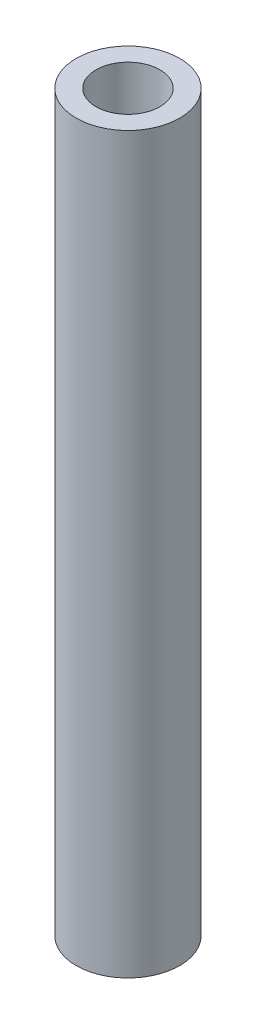
SolidWorks part; units mm, degrees
material "6063-T6"
ref_plane "Front Plane" through (0, 0, 0) normal (0, 0, 1) x (1, 0, 0)
ref_plane "Top Plane" through (0, 0, 0) normal (0, 1, 0) x (1, 0, 0)
ref_plane "Right Plane" through (0, 0, 0) normal (1, 0, 0) x (0, 0, -1)
sketch "Sketch1" plane through (0, 0, 0) normal (0, 1, 0) x (1, 0, 0)
  circle A0 centre (0, 0) radius 2.58
  circle A1 centre (0, 0) radius 5.5
  circle A2 centre (0, 0) radius 4.58 construction
  dimension "D1" = 2
  dimension "D2" = 11
  dimension "D3" = 5.16
  dimension "D4" = 9.16
extrude "Boss-Extrude1" add sketch "Sketch1" along normal blind 78
sketch "Sketch2" plane through (0, 0, 0) normal (0, -1, 0) x (1, 0, 0)
  circle A0 centre (0, 0) radius 5.5
  circle A1 centre (0, 0) radius 5.5 construction
  circle A2 centre (0, 0) radius 5.5
  point P2 (0, 0)
  point P3 (5.3485, 1.2822)
  point P4 (0, 0)
  point P5 (0, 0)
  dimension "D1" = 11
sketch "Sketch4" plane through (0, 78, 0) normal (0, 1, 0) x (1, 0, 0)
  circle A0 centre (0, 0) radius 3.4
  circle A2 centre (0, 0) radius 5.5 construction
  point P5 (0, 0)
  point P6 (0, 0)
  circle M3 centre (0, 0) radius 2.58
  dimension "D1" = 6.8
  dimension "D2" = 2.1
extrude "Cut-Extrude2" cut sketch "Sketch4" against normal blind 65 contours A0 M3 region at (-3.3038, 78, 0)
